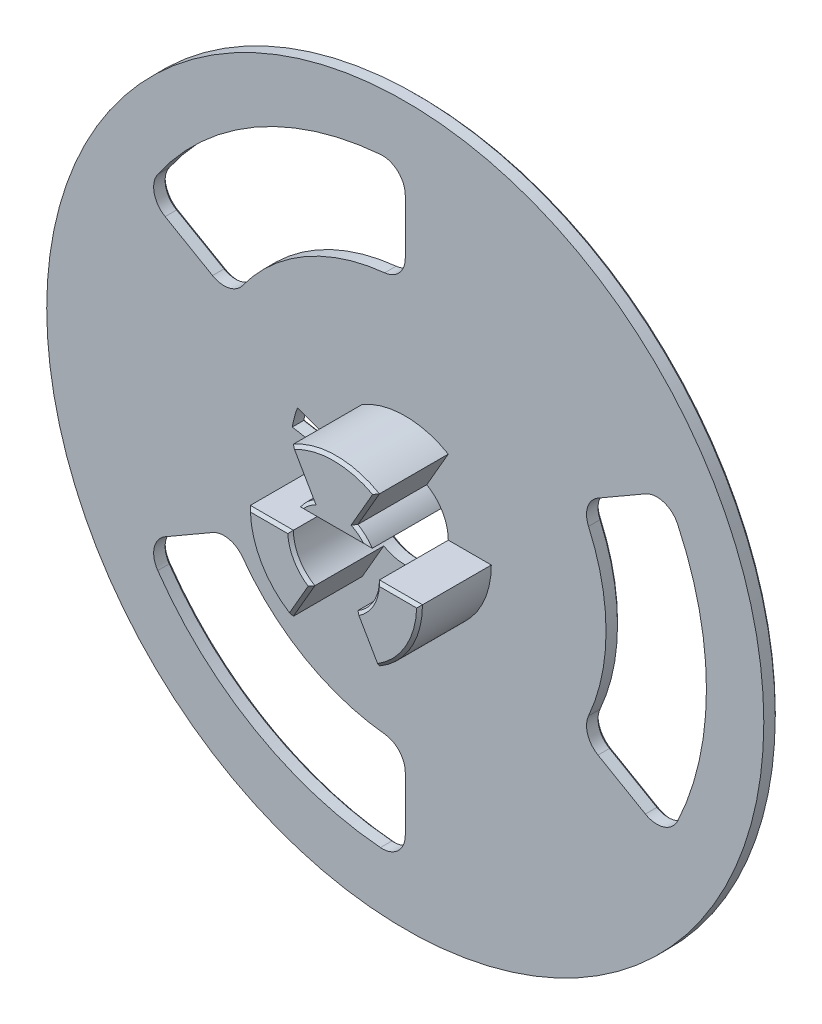
SolidWorks part; units mm, degrees
note: The reader was unsure of these and kept them because the rebuilt part matched: shared geometry of "草图1<5>".
material "ABS"
ref_plane "前视基准面" through (0, 0, 0) normal (0, 0, 1) x (1, 0, 0)
ref_plane "上视基准面" through (0, 0, 0) normal (0, 1, 0) x (1, 0, 0)
ref_plane "右视基准面" through (0, 0, 0) normal (1, 0, 0) x (0, 0, -1)
sketch "草图1" plane through (0, 0, 0) normal (0, 0, 1) x (1, 0, 0)
  line L0 (-2.5, 1.6583) -> (2.5, 1.6583)
  line L1 (-7.8785, 1.3892) -> (-5.9088, 1.0419)
  line L2 (0, 0) -> (-8, 0) construction
  line L3 (-7.5175, 2.7362) -> (-5.6382, 2.0521)
  line L4 (3, 0) -> (6, 0)
  line L5 (1.5, -2.5981) -> (3, -5.1962)
  line L6 (-1.5, -2.5981) -> (-3, -5.1962)
  line L7 (-3, 0) -> (-6, 0)
  line L8 (-1.5, 2.5981) -> (-3, 5.1962)
  line L9 (1.5, 2.5981) -> (3, 5.1962)
  line L10 (0, -14) -> (0, -21)
  line L11 (-12.1244, -7) -> (-18.1865, -10.5)
  line L12 (-12.1244, 7) -> (-18.1865, 10.5)
  line L13 (0, 14) -> (0, 21)
  line L14 (12.1244, 7) -> (18.1865, 10.5)
  line L15 (12.1244, -7) -> (18.1865, -10.5)
  circle A0 centre (0, 0) radius 3
  circle A2 centre (0, 0) radius 25
  arc A3 (3, 5.1962) -> (-3, 5.1962) centre (0, 0) ccw
  circle A4 centre (0, 0) radius 8
  arc A5 (0, 14) -> (-12.1244, 7) centre (0, 0) ccw
  arc A6 (0, 21) -> (-18.1865, 10.5) centre (0, 0) ccw
  arc A7 (18.1865, -10.5) -> (18.1865, 10.5) centre (0, 0) ccw
  arc A8 (12.1244, -7) -> (12.1244, 7) centre (0, 0) ccw
  arc A9 (-18.1865, -10.5) -> (0, -21) centre (0, 0) ccw
  arc A10 (-12.1244, -7) -> (0, -14) centre (0, 0) ccw
  arc A11 (3, -5.1962) -> (6, 0) centre (0, 0) ccw
  arc A12 (-5.6382, 2.0521) -> (-5.9088, 1.0419) centre (0, 0) ccw
  arc A13 (-6, 0) -> (-3, -5.1962) centre (0, 0) ccw
  point P28 (0, 0)
  point P30 (0, 0)
  point P42 (0, 0)
  dimension "D1" = 6
  dimension "D3" = 6
  dimension "D4" = 50
  dimension "D7" = 16
  dimension "D8" = 12
  dimension "D10" = 28
  dimension "D11" = 42
  dimension "D2" = 5
  dimension "D5" = 10
  dimension "D6" = 20
  dimension "D9" = 6
extrude "凸台-拉伸1" add sketch "草图1" against normal blind 1
fillet "圆角1" radius 1.6 12 edges at (-18.1865, -10.5, -0.5) (-12.1244, -7, -0.5) (0, -14, -0.5) (0, -21, -0.5) (18.1865, -10.5, -0.5) (18.1865, 10.5, -0.5) (12.1244, 7, -0.5) (12.1244, -7, -0.5) (-18.1865, 10.5, -0.5) (-12.1244, 7, -0.5) (0, 14, -0.5) (0, 21, -0.5)
extrude "凸台-拉伸3" add sketch "草图1<5>" along normal blind 5 contours L0 A0 | L9 A3 L8 A0 | L7 A3 L6 A0 | L5 A3 L4 A0
sketch "草图1<5>" plane through (0, 0, 0) normal (0, 0, 1) x (1, 0, 0) same geometry as "草图1"
chamfer "倒角3" distance 0.2 angle 45 45 edges at (-0.412, -14.4459, -1) (0, -17.4258, -1) (-0.5163, -20.511, -1) (-10.5, -18.1865, -1) (-17.5049, -10.7026, -1) (-15.0912, -8.7129, -1) (-12.3045, -7.5798, -1) (-7, -12.1244, -1) (12.7166, 6.8661, -1) (15.0912, 8.7129, -1) (18.0212, 9.8084, -1) (21, 0, -1) (18.0212, -9.8084, -1) (15.0912, -8.7129, -1) (12.7166, -6.8661, -1) (14, 0, -1) (25, 0, -1) (-0.412, 14.4459, -1) (-7, 12.1244, -1) (-12.3045, 7.5798, -1) (-15.0912, 8.7129, -1) (-17.5049, 10.7026, -1) (-10.5, 18.1865, -1) (-0.5163, 20.511, -1) (0, 17.4258, -1) (-6.5778, 2.3941, -1) (-5.7956, 1.5529, -1) (-6.8937, 1.2155, -1) (-7.7274, 2.0706, -1) (0, 1.6583, 5) (0, 1.6583, -1) (0, -3, -1) (-2.5981, -1.5, 5) (-2.25, -3.8971, 5) (-5.1962, -3, 5) (-4.5, 0, 5) (2.5981, -1.5, 5) (4.5, 0, 5) (5.1962, -3, 5) (2.25, -3.8971, 5) (-2.0545, 2.1861, 5) (-2.25, 3.8971, 5) (0, 6, 5) (2.25, 3.8971, 5) (2.0545, 2.1861, 5)
